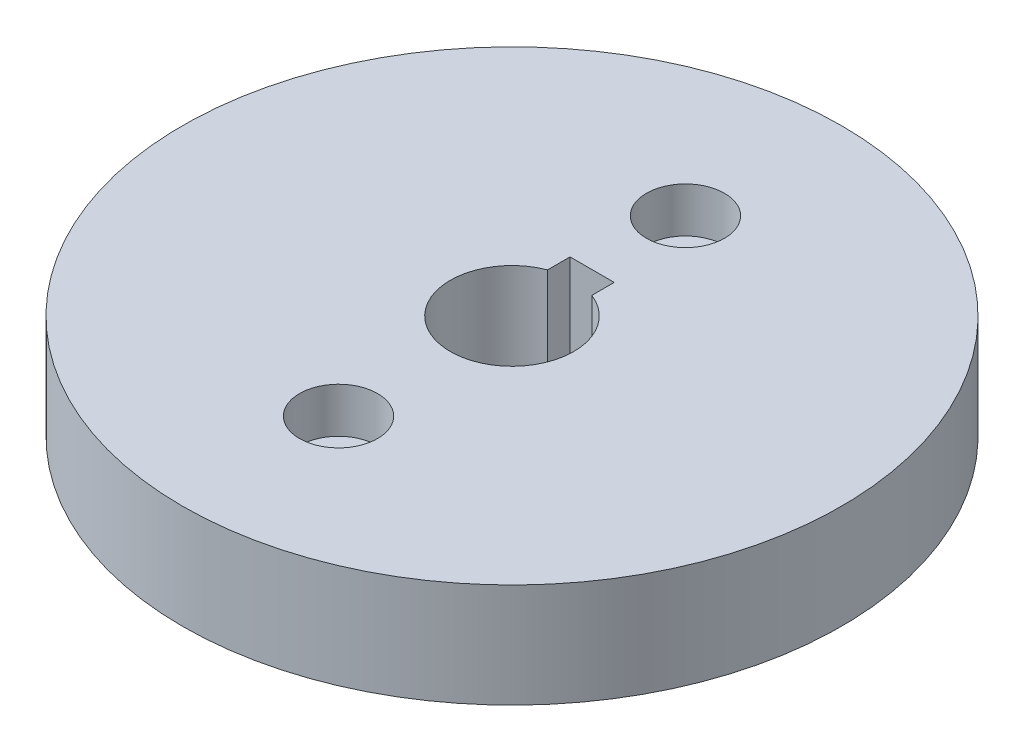
SolidWorks part; units mm, degrees
ref_plane "Front Plane" through (0, 0, 0) normal (0, 0, 1) x (1, 0, 0)
ref_plane "Top Plane" through (0, 0, 0) normal (0, 1, 0) x (1, 0, 0)
ref_plane "Right Plane" through (0, 0, 0) normal (1, 0, 0) x (0, 0, -1)
sketch "Sketch1" plane through (0, 0, 0) normal (0, 1, 0) x (1, 0, 0)
  circle A0 centre (0, 0) radius 38
extrude "Boss-Extrude1" add sketch "Sketch1" along normal blind 12
sketch "Sketch2" plane through (0, 12, 0) normal (0, 1, 0) x (1, 0, 0)
  circle A0 centre (0, 20) radius 2.75
  circle A1 centre (0, -20) radius 2.75
  dimension "D1" = 20
  dimension "D2" = 20
extrude "Cut-Extrude1" cut sketch "Sketch2" against normal blind 25
sketch "Sketch3" plane through (0, 12, 0) normal (0, 1, 0) x (1, 0, 0)
  circle A1 centre (0, 20) radius 4.5
  circle A2 centre (0, -20) radius 4.5
sketch "Sketch4" plane through (0, 12, 0) normal (0, 1, 0) x (1, 0, 0)
  line L0 (0, 7.12) -> (0, 9.24)
  line L1 (0, 9.24) -> (-2.55, 9.24)
  line L2 (0, 9.24) -> (2.55, 9.24)
  line L3 (-2.55, 9.24) -> (-2.55, 6.6477)
  line L4 (2.55, 9.24) -> (2.55, 6.6477)
  circle A0 centre (0, 0) radius 7.12
extrude "Cut-Extrude3" cut sketch "Sketch3" against normal blind 5.2
extrude "Cut-Extrude4" cut sketch "Sketch4" against normal blind 27 contours A0 L0 L1 L3 | A0 L4 L2 L0 | A0 region at (-1.3188, 12, -8.098) region at (1.3188, 12, -8.098) region at (0, 12, 0)
